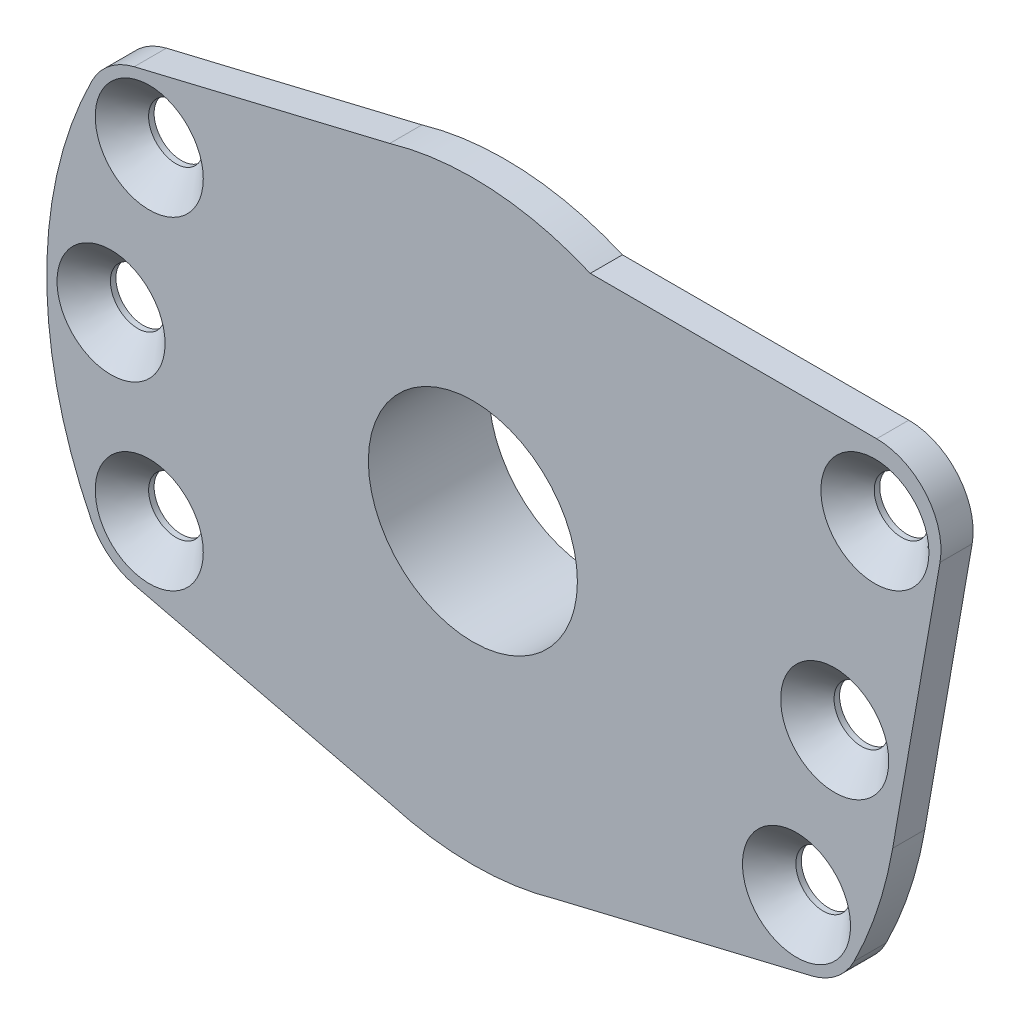
SolidWorks part; units mm, degrees
ref_plane "Спереди" through (0, 0, 0) normal (0, 0, 1) x (1, 0, 0)
ref_plane "Сверху" through (0, 0, 0) normal (0, 1, 0) x (1, 0, 0)
ref_plane "Справа" through (0, 0, 0) normal (1, 0, 0) x (0, 0, -1)
sketch "Эскиз1" plane through (0, 0, 0) normal (0, 0, 1) x (1, 0, 0)
  line L0 (-9.3783, -4.6892) -> (44711.9812, 22355.9906) construction
  line L1 (0, 0.385) -> (0, 50000.385) construction
  line L2 (-11.9154, 0) -> (49988.0846, 0) construction
  line L3 (0, 0) -> (-44721.3595, 22360.6798) construction
  line L4 (-5.1682, 17.7645) -> (-21.0579, 13.9519)
  line L5 (-5.1682, -17.7645) -> (-21.0579, -13.9519)
  line L6 (5.1682, -17.7645) -> (21.0579, -13.9519)
  line L7 (29.0494, 12.3123) -> (26.1054, -4.5561)
  line L8 (25.109, 17) -> (7.3, 17)
  arc A0 (-23.7023, 11.8512) -> (-23.7023, -11.8512) centre (0, 0) ccw
  arc A1 (-23.7023, 11.8512) -> (-21.0579, 13.9519) centre (-20.1246, 10.0623) cw
  arc A2 (7.3, 17) -> (-5.1682, 17.7645) centre (0, 0) ccw
  circle A3 centre (0, 0) radius 22.5 construction
  arc A4 (-23.7023, -11.8512) -> (-21.0579, -13.9519) centre (-20.1246, -10.0623) ccw
  arc A5 (23.7023, -11.8512) -> (21.0579, -13.9519) centre (20.1246, -10.0623) cw
  arc A6 (-5.1682, -17.7645) -> (5.1682, -17.7645) centre (0, 0) ccw
  arc A7 (26.1054, -4.5561) -> (23.7023, -11.8512) centre (0, 0) cw
  circle A9 centre (25, 12.5) radius 0.5
  circle A10 centre (22.5, 0) radius 0.5
  circle A11 centre (20.1246, -10.0623) radius 0.5
  circle A12 centre (-20.1246, -10.0623) radius 0.5
  circle A13 centre (-22.5, 0) radius 0.5
  circle A14 centre (-20.1246, 10.0623) radius 0.5
  circle A15 centre (0, 0) radius 6.5
  arc A16 (25.109, 17) -> (29.0494, 12.3123) centre (25.109, 13) cw
  point P38 (0, 0)
  point P39 (0, 0)
  dimension "D1" = 53
  dimension "D2" = 4
  dimension "D3" = 45
  dimension "D4" = 18.5011
  dimension "D6" = 17
  dimension "D10" = 1
  dimension "D11" = 1
  dimension "D12" = 1
  dimension "D13" = 1
  dimension "D14" = 13
  dimension "D15" = 4
  dimension "D7" = 53.13
  dimension "D8" = 25
  dimension "D9" = 12.5
  dimension "D16" = 99.9
  dimension "D5" = 49.942
extrude "Бобышка-Вытянуть2" add sketch "Эскиз1" along normal blind 2
hole_wizard "Зенковка для винта с потайной головкой и внутренним шестигранником M31" positions "Эскиз2" profile "Эскиз3" countersink size "M3" standard "ISO" end condition through all
sketch "Эскиз2" plane through (0, 0, 2) normal (0, 0, 1) x (1, 0, 0)
  point P0 (-20.1246, 10.0623)
  point P3 (-22.5, 0)
  point P6 (-20.1246, -10.0623)
  point P9 (20.1246, -10.0623)
  point P12 (22.5, 0)
  point P15 (25, 12.5)
sketch "Эскиз3" plane through (-20.1246, 10.0623, 2) normal (1, 0, 0) x (0, -1, 0)
  line L0 (0, 0) -> (0, 2)
  line L1 (0, 2) -> (1.7, 2)
  line L2 (1.7, 2) -> (1.7, 1.66)
  line L3 (1.7, 1.66) -> (3.36, 0)
  line L5 (3.36, 0) -> (0, 0)
  line L6 (-1.7, 1.66) -> (-3.36, 0) construction
  line L11 (0, -6.35) -> (0, 107.95) construction
  dimension "Диаметр сквозного отверстия" = 3.4
  dimension "Глубина сквозного отверстия" = 2
  dimension "Диаметр передней зенковки" = 6.72
  dimension "Угол передней зенковки" = 90
sketch "Эскиз4" plane through (0, 0, 0) normal (0, 0, -1) x (-1, 0, 0)
  circle A0 centre (0, 0) radius 8.5
  circle A1 centre (0, 0) radius 6.5
  dimension "D1" = 17
  dimension "D2" = 13
extrude "Бобышка-Вытянуть3" add sketch "Эскиз4" along normal blind 0.5
sketch "Эскиз5" plane through (0, 0, -0.5) normal (0, 0, -1) x (-1, 0, 0)
  circle A0 centre (0, 0) radius 6.5
  circle A1 centre (0, 0) radius 7.5
  dimension "D1" = 13
  dimension "D2" = 15
extrude "Бобышка-Вытянуть4" add sketch "Эскиз5" along normal blind 5
